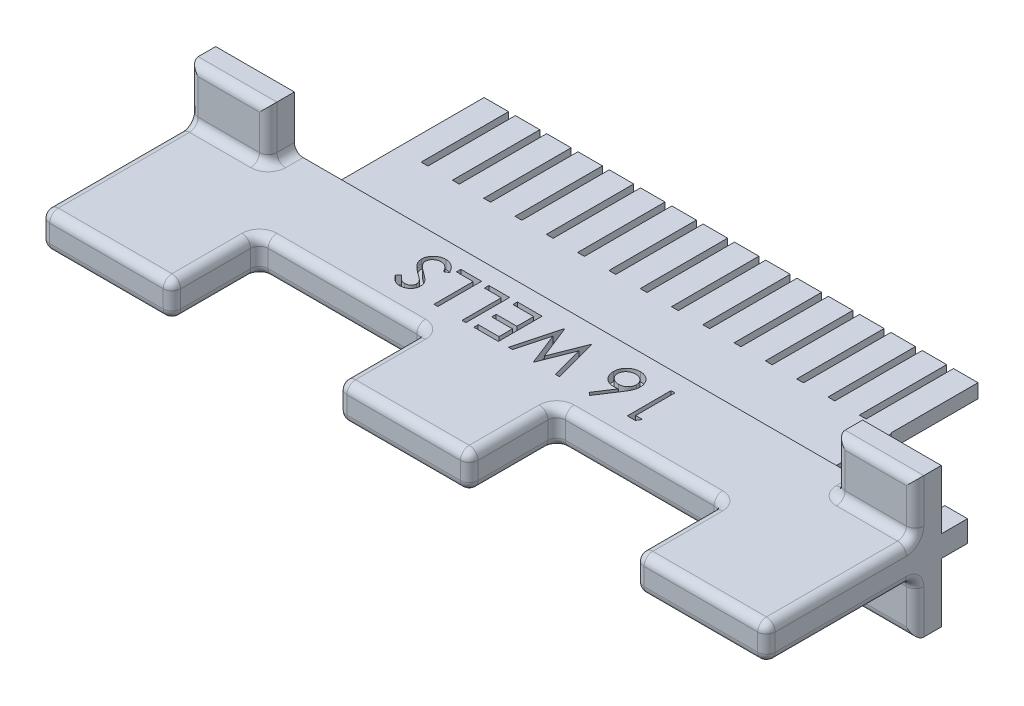
SolidWorks part; units mm, degrees
ref_plane "Front Plane" through (0, 0, 0) normal (0, 0, 1) x (1, 0, 0)
ref_plane "Top Plane" through (0, 0, 0) normal (0, 1, 0) x (1, 0, 0)
ref_plane "Right Plane" through (0, 0, 0) normal (1, 0, 0) x (0, 0, -1)
sketch "Sketch1" plane through (0, 0, 0) normal (0, 0, 1) x (1, 0, 0)
  line L1 (-41.5, 2) -> (41.5, 2)
  line L2 (-41.5, 2) -> (-41.5, -2)
  line L3 (-41.5, -2) -> (41.5, -2)
  line L4 (41.5, 2) -> (41.5, -2)
  line L5 (-41.5, 2) -> (41.5, -2) construction
  line L6 (-41.5, -2) -> (41.5, 2) construction
  point P0 (0, 0)
  dimension "D1" = 83
  dimension "D2" = 4
extrude "Boss-Extrude1" add sketch "Sketch1" along normal blind 10
sketch "Sketch2" plane through (0, 0, 10) normal (0, 0, 1) x (1, 0, 0)
  line L0 (-41.5, -2) -> (41.5, -2) construction
  line L1 (-41.5, 2) -> (-26.5, 2)
  line L2 (-41.5, 2) -> (-41.5, -2)
  line L3 (-41.5, -2) -> (-26.5, -2)
  line L4 (-26.5, 2) -> (-26.5, -2)
  line L6 (41.5, 2) -> (26.5, 2)
  line L7 (41.5, 2) -> (41.5, -2)
  line L8 (41.5, -2) -> (26.5, -2)
  line L9 (26.5, 2) -> (26.5, -2)
  line L10 (-7.5, 2) -> (7.5, 2)
  line L11 (-7.5, 2) -> (-7.5, -2)
  line L12 (-7.5, -2) -> (7.5, -2)
  line L13 (7.5, 2) -> (7.5, -2)
  line L14 (-7.5, 2) -> (7.5, -2) construction
  line L15 (-7.5, -2) -> (7.5, 2) construction
  point P12 (0, 0)
  dimension "D1" = 15
extrude "Boss-Extrude2" add sketch "Sketch2" along normal blind 10
sketch "Sketch3" plane through (0, 0, 0) normal (0, 0, -1) x (-1, 0, 0)
  line L9 (41.5, -1.225) -> (38.9, -1.225)
  line L10 (41.5, -1.225) -> (41.5, 1.225)
  line L11 (41.5, 1.225) -> (38.9, 1.225)
  line L12 (38.9, -1.225) -> (38.9, 1.225)
  line L13 (41.5, -1.225) -> (38.9, 1.225) construction
  line L14 (41.5, 1.225) -> (38.9, -1.225) construction
  line L15 (41.5, 2) -> (41.5, -2) construction
  line L16 (0, 0) -> (0, 13.9589)
  line L17 (-41.5, 1.225) -> (-38.9, -1.225) construction
  line L18 (-41.5, -1.225) -> (-38.9, 1.225) construction
  line L19 (-38.9, -1.225) -> (-38.9, 1.225)
  line L20 (-41.5, 1.225) -> (-38.9, 1.225)
  line L21 (-41.5, -1.225) -> (-41.5, 1.225)
  line L22 (-41.5, -1.225) -> (-38.9, -1.225)
  point P3 (41.5, 0)
  point P10 (40.2, 0)
  point P16 (-40.2, 0)
  line M3 (-41.5, 2) -> (-41.5, -2)
  dimension "D1" = 2.45
  dimension "D2" = 2.6
extrude "Boss-Extrude3" add sketch "Sketch3" along normal blind 3 contours L22 L19 L20 M3 | L12 L11 L10 L9 region at (40.2, 0, 0)
sketch "Sketch4" plane through (0, 0, 0) normal (0, 0, -1) x (-1, 0, 0)
  line L0 (-41.5, -2) -> (-41.5, -1.225) construction
  line L1 (28.3, -0.8) -> (-28.3, -0.8)
  line L2 (28.3, -0.8) -> (28.3, 0.8)
  line L3 (28.3, 0.8) -> (-28.3, 0.8)
  line L4 (-28.3, -0.8) -> (-28.3, 0.8)
  line L5 (28.3, -0.8) -> (-28.3, 0.8) construction
  line L6 (28.3, 0.8) -> (-28.3, -0.8) construction
  point P0 (0, 0)
  dimension "D1" = 1.6
  dimension "D2" = 13.2
extrude "Boss-Extrude4" add sketch "Sketch4" along normal blind 7.5
sketch "Sketch5" plane through (0, 0, -7.5) normal (0, 0, -1) x (-1, 0, 0)
  line L0 (28.3, 0.8) -> (-28.3, 0.8) construction
  line L1 (28.3, -0.8) -> (25.5, -0.8)
  line L2 (28.3, -0.8) -> (28.3, 0.8)
  line L3 (28.3, 0.8) -> (25.5, 0.8)
  line L4 (25.5, -0.8) -> (25.5, 0.8)
  line L33 (24.72, -0.8) -> (21.92, -0.8)
  line L34 (24.72, -0.8) -> (24.72, 0.8)
  line L35 (24.72, 0.8) -> (21.92, 0.8)
  line L36 (21.92, -0.8) -> (21.92, 0.8)
  line L37 (21.14, -0.8) -> (18.34, -0.8)
  line L38 (21.14, -0.8) -> (21.14, 0.8)
  line L39 (21.14, 0.8) -> (18.34, 0.8)
  line L40 (18.34, -0.8) -> (18.34, 0.8)
  line L41 (17.56, -0.8) -> (14.76, -0.8)
  line L42 (17.56, -0.8) -> (17.56, 0.8)
  line L43 (17.56, 0.8) -> (14.76, 0.8)
  line L44 (14.76, -0.8) -> (14.76, 0.8)
  line L45 (13.98, -0.8) -> (11.18, -0.8)
  line L46 (13.98, -0.8) -> (13.98, 0.8)
  line L47 (13.98, 0.8) -> (11.18, 0.8)
  line L48 (11.18, -0.8) -> (11.18, 0.8)
  line L49 (10.4, -0.8) -> (7.6, -0.8)
  line L50 (10.4, -0.8) -> (10.4, 0.8)
  line L51 (10.4, 0.8) -> (7.6, 0.8)
  line L52 (7.6, -0.8) -> (7.6, 0.8)
  line L53 (6.8201, -0.8) -> (4.0201, -0.8)
  line L54 (6.8201, -0.8) -> (6.8201, 0.8)
  line L55 (6.8201, 0.8) -> (4.0201, 0.8)
  line L56 (4.0201, -0.8) -> (4.0201, 0.8)
  line L57 (3.2401, -0.8) -> (0.4401, -0.8)
  line L58 (3.2401, -0.8) -> (3.2401, 0.8)
  line L59 (3.2401, 0.8) -> (0.4401, 0.8)
  line L60 (0.4401, -0.8) -> (0.4401, 0.8)
  line L61 (-0.3399, -0.8) -> (-3.1399, -0.8)
  line L62 (-0.3399, -0.8) -> (-0.3399, 0.8)
  line L63 (-0.3399, 0.8) -> (-3.1399, 0.8)
  line L64 (-3.1399, -0.8) -> (-3.1399, 0.8)
  line L65 (-3.9199, -0.8) -> (-6.7199, -0.8)
  line L66 (-3.9199, -0.8) -> (-3.9199, 0.8)
  line L67 (-3.9199, 0.8) -> (-6.7199, 0.8)
  line L68 (-6.7199, -0.8) -> (-6.7199, 0.8)
  line L69 (-7.4999, -0.8) -> (-10.2999, -0.8)
  line L70 (-7.4999, -0.8) -> (-7.4999, 0.8)
  line L71 (-7.4999, 0.8) -> (-10.2999, 0.8)
  line L72 (-10.2999, -0.8) -> (-10.2999, 0.8)
  line L73 (-11.0799, -0.8) -> (-13.8799, -0.8)
  line L74 (-11.0799, -0.8) -> (-11.0799, 0.8)
  line L75 (-11.0799, 0.8) -> (-13.8799, 0.8)
  line L76 (-13.8799, -0.8) -> (-13.8799, 0.8)
  line L77 (-14.6599, -0.8) -> (-17.4599, -0.8)
  line L78 (-14.6599, -0.8) -> (-14.6599, 0.8)
  line L79 (-14.6599, 0.8) -> (-17.4599, 0.8)
  line L80 (-17.4599, -0.8) -> (-17.4599, 0.8)
  line L81 (-18.2399, -0.8) -> (-21.0399, -0.8)
  line L82 (-18.2399, -0.8) -> (-18.2399, 0.8)
  line L83 (-18.2399, 0.8) -> (-21.0399, 0.8)
  line L84 (-21.0399, -0.8) -> (-21.0399, 0.8)
  line L85 (-21.8199, -0.8) -> (-24.6199, -0.8)
  line L86 (-21.8199, -0.8) -> (-21.8199, 0.8)
  line L87 (-21.8199, 0.8) -> (-24.6199, 0.8)
  line L88 (-24.6199, -0.8) -> (-24.6199, 0.8)
  line L89 (-25.3999, -0.8) -> (-28.1999, -0.8)
  line L90 (-25.3999, -0.8) -> (-25.3999, 0.8)
  line L91 (-25.3999, 0.8) -> (-28.1999, 0.8)
  line L92 (-28.1999, -0.8) -> (-28.1999, 0.8)
  dimension "D2" = 2.8
  dimension "D1" = 16
extrude "Boss-Extrude5" add sketch "Sketch5" along normal blind 10
sketch "Sketch6" plane through (0, 0, 0) normal (0, 0, -1) x (-1, 0, 0)
  line L1 (41.5, -2) -> (32.5, -2)
  line L2 (41.5, -2) -> (41.5, -8)
  line L3 (41.5, -8) -> (32.5, -8)
  line L4 (32.5, -2) -> (32.5, -8)
  line L5 (41.5, 2) -> (32.5, 2)
  line L6 (41.5, 2) -> (41.5, 8)
  line L7 (41.5, 8) -> (32.5, 8)
  line L8 (32.5, 2) -> (32.5, 8)
  line L9 (-41.5, -2) -> (-32.5, -2)
  line L10 (-41.5, -2) -> (-41.5, -8)
  line L11 (-41.5, -8) -> (-32.5, -8)
  line L12 (-32.5, -2) -> (-32.5, -8)
  line L13 (-41.5, 2) -> (-32.5, 2)
  line L14 (-41.5, 2) -> (-41.5, 8)
  line L15 (-41.5, 8) -> (-32.5, 8)
  line L16 (-32.5, 2) -> (-32.5, 8)
  dimension "D1" = 6
  dimension "D2" = 9
extrude "Boss-Extrude6" add sketch "Sketch6" against normal blind 3
fillet "Fillet1" radius 1 52 edges at (-41.5, -2, 11.5) (-32.5, -2, 1.5) (-37, -2, 3) (-32.5, -5, 3) (-37, -8, 3) (-41.5, -5, 3) (-26.5, 0, 20) (-34, -2, 20) (-41.5, 0, 20) (-34, 2, 20) (32.5, -2, 1.5) (41.5, -2, 11.5) (41.5, 2, 11.5) (32.5, 2, 1.5) (-32.5, 2, 1.5) (-41.5, 2, 11.5) (37, -8, 3) (32.5, -5, 3) (37, -2, 3) (41.5, -5, 3) (34, -2, 20) (26.5, 0, 20) (34, 2, 20) (41.5, 0, 20) (37, 2, 3) (32.5, 5, 3) (37, 8, 3) (41.5, 5, 3) (0, -2, 20) (-7.5, 0, 20) (0, 2, 20) (7.5, 0, 20) (-37, 8, 3) (-32.5, 5, 3) (-37, 2, 3) (-41.5, 5, 3) (26.5, 2, 15) (26.5, -2, 15) (26.5, 0, 10) (17, -2, 10) (17, 2, 10) (7.5, -2, 15) (7.5, 2, 15) (7.5, 0, 10) (-7.5, 2, 15) (-7.5, -2, 15) (-26.5, -2, 15) (-26.5, 2, 15) (-26.5, 0, 10) (-17, 2, 10) (-7.5, 0, 10) (-17, -2, 10)
ref_plane "Plane1" through (0, 0, 0) normal (0, 1, 0) x (1, 0, 0)
sketch "Sketch7" plane through (0, 2, 0) normal (0, 1, 0) x (1, 0, 0)
  line L0 (30.9142, -2.045) -> (-30.9142, -2.045)
  line L1 (31.5, 0) -> (-31.5, 0) construction
  point P2 (0, -2.045)
  point P5 (0, 0)
sketch "Sketch8" plane through (0, 2, 0) normal (0, 1, 0) x (1, 0, 0)
  text T0 "16 WELLS" font "Century Gothic" height 5
extrude "Cut-Extrude1" cut sketch "Sketch8" against normal blind 1
